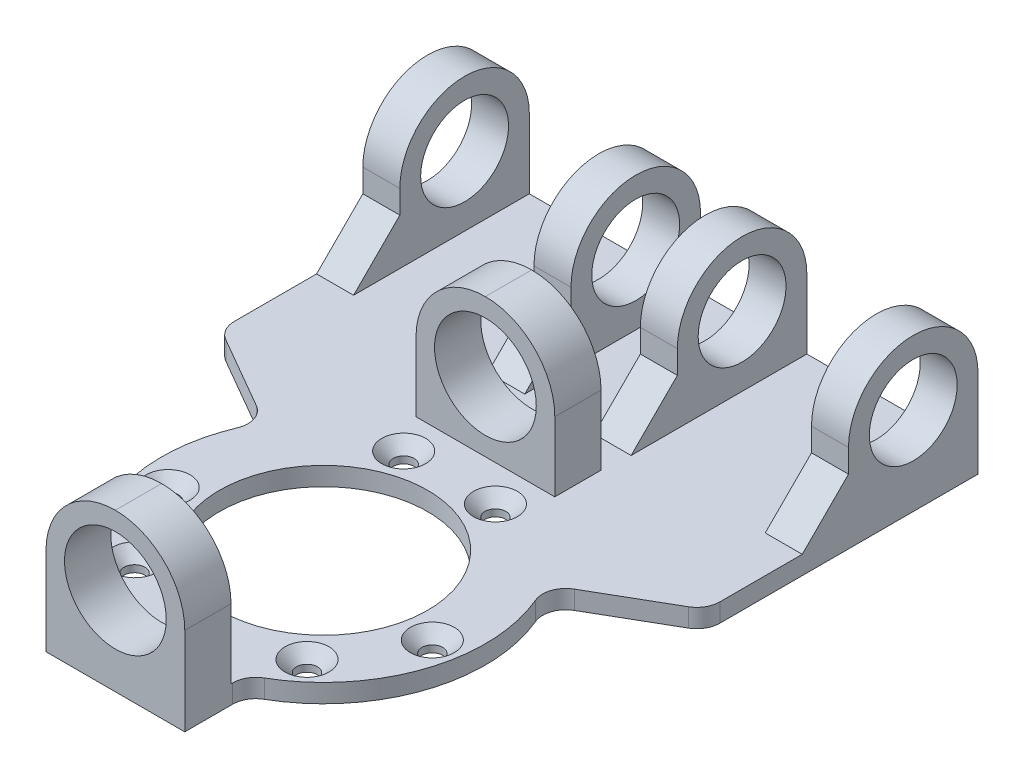
SolidWorks part; units mm, degrees
ref_plane "前视基准面" through (0, 0, 0) normal (0, 0, 1) x (1, 0, 0)
ref_plane "上视基准面" through (0, 0, 0) normal (0, 1, 0) x (1, 0, 0)
ref_plane "右视基准面" through (0, 0, 0) normal (1, 0, 0) x (0, 0, -1)
other "Configuration Table"
sketch "草图1" plane through (0, 0, 0) normal (0, 1, 0) x (1, 0, 0)
  line L0 (0, 0) -> (0, 35) construction
  line L1 (0, 0) -> (11.9707, 32.8892) construction
  line L2 (0, 0) -> (-11.9707, 32.8892) construction
  circle A0 centre (0, 0) radius 22.5
  circle A1 centre (0, 0) radius 35
  circle A2 centre (0, 0) radius 29 construction
  circle A3 centre (-9.9186, 27.2511) radius 2.25
  circle A4 centre (9.9186, 27.2511) radius 2.25
  circle A5 centre (28.5594, -5.0358) radius 2.25
  circle A6 centre (18.6408, -22.2153) radius 2.25
  circle A7 centre (-18.6408, -22.2153) radius 2.25
  circle A8 centre (-28.5594, -5.0358) radius 2.25
  point P6 (9.9186, 27.2511)
  point P8 (-9.9186, 27.2511)
  point P10 (18.6408, -22.2153)
  point P13 (28.5594, -5.0358)
  point P14 (-28.5594, -5.0358)
  point P15 (-18.6408, -22.2153)
  point P16 (0, 0)
  dimension "D1" = 58
  dimension "D2" = 45
  dimension "D3" = 70
  dimension "D6" = 4.5
  dimension "D4" = 20
  dimension "D5" = 3
extrude "凸台-拉伸1" add sketch "草图1" along normal blind 4
sketch "草图2" plane through (0, 0, 0) normal (0, 1, 0) x (1, 0, 0)
  line L0 (0, 0) -> (0, -45) construction
  line L1 (15, -42.4264) -> (15, -31.6228)
  line L2 (-15, -42.4264) -> (-15, -31.6228)
  arc A0 (-15, -42.4264) -> (15, -42.4264) centre (0, 0) ccw
  circle A1 centre (0, 0) radius 35 construction
  arc A2 (-15, -31.6228) -> (15, -31.6228) centre (0, 0) ccw
  dimension "D1" = 90
  dimension "D2" = 30
extrude "凸台-拉伸2" add sketch "草图2" along normal blind 4
sketch "草图3" plane through (0, 0, 0) normal (0, 1, 0) x (1, 0, 0)
  line L0 (-15, -45) -> (15, -45)
  line L1 (15, -45) -> (15, -35)
  line L2 (15, -35) -> (-15, -35)
  line L3 (0, -35) -> (0, -45) construction
  line L4 (-15, -45) -> (-15, -35)
  arc A0 (-15, -42.4264) -> (15, -42.4264) centre (0, 0) ccw construction
  circle A1 centre (0, 0) radius 35 construction
  dimension "D1" = 30
extrude "凸台-拉伸3" add sketch "草图3" along normal blind 34
mirror "镜向1" about plane through (0, 0, 0) normal (0, 0, 1) of "凸台-拉伸3", "凸台-拉伸2"
sketch "草图4" plane through (0, 0, 0) normal (0, 1, 0) x (1, 0, 0)
  line L0 (0, 0) -> (0, 89) construction
  line L1 (-52.5, 89) -> (52.5, 89)
  line L2 (52.5, 89) -> (52.5, 30.3109)
  line L3 (52.5, 30.3109) -> (30.3109, 17.5)
  line L4 (-15, 45) -> (15, 45) construction
  line L5 (-52.5, 30.3109) -> (-30.3109, 17.5)
  line L6 (-52.5, 89) -> (-52.5, 30.3109)
  line L7 (52.5, 30.3109) -> (0, 0) construction
  circle A0 centre (0, 0) radius 35 construction
  arc A1 (30.3109, 17.5) -> (-30.3109, 17.5) centre (0, 0) ccw
  dimension "D1" = 60
  dimension "D2" = 44
  dimension "D3" = 105
extrude "凸台-拉伸4" add sketch "草图4" along normal blind 4
sketch "草图5" plane through (0, 0, 0) normal (1, 0, 0) x (0, 0, -1)
  line L0 (89, 4) -> (61, 4)
  line L1 (30.3109, 4) -> (89, 4) construction
  line L2 (61, 4) -> (61, 19)
  line L3 (61, 19) -> (89, 19) construction
  line L4 (89, 19) -> (89, 4)
  arc A0 (89, 19) -> (61, 19) centre (75, 19) ccw
  circle A1 centre (75, 19) radius 9.5
  dimension "D3" = 19
  dimension "D1" = 28
  dimension "D2" = 15
extrude "凸台-拉伸5" add sketch "草图5" along normal mid plane 105
sketch "草图6" plane through (0, 0, -89) normal (0, 0, -1) x (-1, 0, 0)
  line L0 (-52.5, 0) -> (52.5, 0) construction
  line L1 (-44.5, 4) -> (-15.5, 4)
  line L2 (-44.5, 4) -> (-44.5, 33)
  line L3 (-44.5, 33) -> (-15.5, 33)
  line L4 (-15.5, 4) -> (-15.5, 33)
  line L5 (-7.5, 4) -> (7.5, 4)
  line L6 (-7.5, 4) -> (-7.5, 33)
  line L7 (-7.5, 33) -> (7.5, 33)
  line L8 (7.5, 4) -> (7.5, 33)
  line L9 (15.5, 4) -> (44.5, 4)
  line L10 (15.5, 4) -> (15.5, 33)
  line L11 (15.5, 33) -> (44.5, 33)
  line L12 (44.5, 4) -> (44.5, 33)
  line L13 (52.5, 19) -> (52.5, 0) construction
  line L14 (52.5, 33) -> (-52.5, 33) construction
  dimension "D1" = 8
  dimension "D2" = 15
  dimension "D3" = 8
  dimension "D4" = 29
  dimension "D5" = 29
  dimension "D6" = 4
  dimension "D7" = 8
extrude "切除-拉伸1" cut sketch "草图6" against normal up to surface (28 mm away) up to face at (0, 11.5, -61)
sketch "草图7" plane through (0, 0, 45) normal (0, 0, 1) x (1, 0, 0)
  line L0 (0, 0) -> (0, 34) construction
  line L1 (-15, 34) -> (15, 34) construction
  line L2 (15, 4) -> (-15, 4) construction
  line L3 (-15, 4) -> (-35, 4) construction
  line L4 (-15, 34) -> (-15, 0) construction
  line L5 (15, 34) -> (15, 0) construction
  circle A0 centre (0, 19) radius 11
  dimension "D2" = 22
  dimension "D1" = 15
extrude "切除-拉伸2" cut sketch "草图7" against normal up to surface (90 mm away) up to face at (0, 19, -45)
fillet "圆角1" radius 15 4 edges at (15, 34, -40) (-15, 34, -40) (-15, 34, 40) (15, 34, 40)
fillet "圆角3" radius 5 6 edges at (-52.5, 2, -30.3109) (52.5, 2, -30.3109) (-15, 2, 31.6228) (-30.3109, 2, -17.5) (30.3109, 2, -17.5) (15, 2, 31.6228)
chamfer "倒角1" distance 2.5 angle 45 6 edges at (-28.5594, 4, 7.2858) (-9.9186, 4, -25.0011) (9.9186, 4, -25.0011) (28.5594, 4, 7.2858) (-18.6408, 4, 24.4653) (18.6408, 4, 24.4653)
chamfer "倒角2" distance 10 angle 45 4 edges at (48.5, 4, -61) (-48.5, 4, -61) (11.5, 4, -61) (-11.5, 4, -61)
